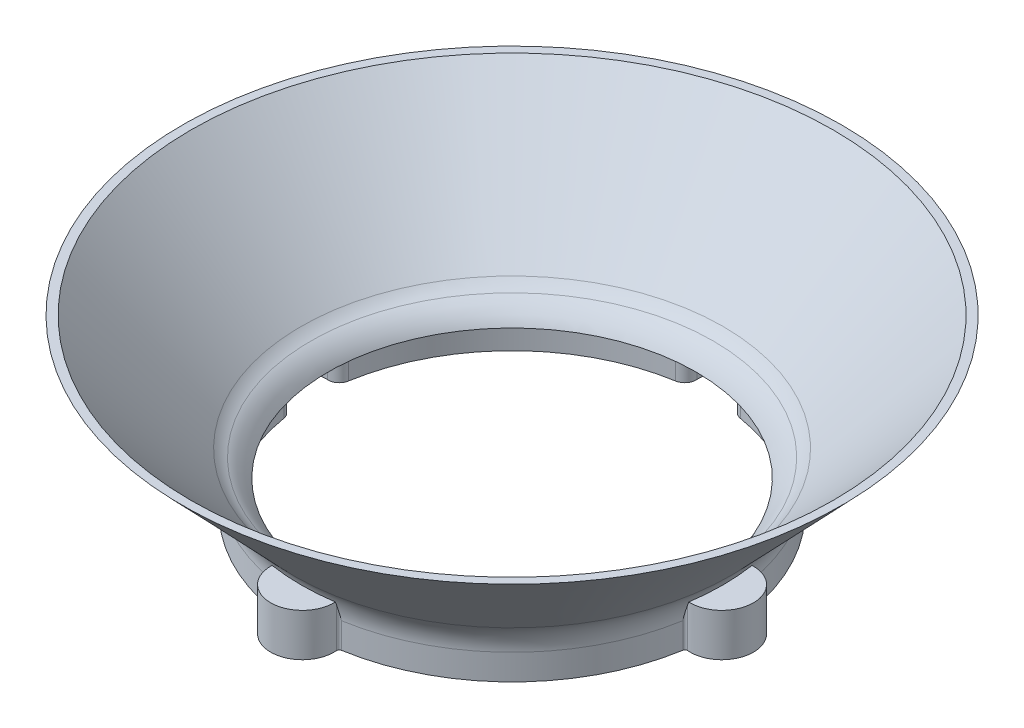
SolidWorks part; units mm, degrees
ref_plane "前视基准面" through (0, 0, 0) normal (0, 0, 1) x (1, 0, 0)
ref_plane "上视基准面" through (0, 0, 0) normal (0, 1, 0) x (1, 0, 0)
ref_plane "右视基准面" through (0, 0, 0) normal (1, 0, 0) x (0, 0, -1)
other "Configuration Table"
sketch "草图1" plane through (0, 0, 0) normal (0, 1, 0) x (1, 0, 0)
  line L0 (-49, 0) -> (0, 0) construction
  circle A0 centre (0, 0) radius 41 construction
  arc A1 (-48.5918, 4.9833) -> (-48.5918, -4.9833) centre (-49, 0) ccw
  circle A2 centre (0, 0) radius 49 construction
  arc A3 (-45.3869, -7.4851) -> (-7.4851, -45.3869) centre (0, 0) ccw
  arc A4 (4.9833, 48.5918) -> (-4.9833, 48.5918) centre (0, 49) ccw
  arc A5 (48.5918, -4.9833) -> (48.5918, 4.9833) centre (49, 0) ccw
  arc A6 (-4.9833, -48.5918) -> (4.9833, -48.5918) centre (0, -49) ccw
  arc A7 (-7.4851, 45.3869) -> (-45.3869, 7.4851) centre (0, 0) ccw
  arc A8 (45.3869, 7.4851) -> (7.4851, 45.3869) centre (0, 0) ccw
  arc A9 (7.4851, -45.3869) -> (45.3869, -7.4851) centre (0, 0) ccw
  arc A10 (-4.9833, -48.5918) -> (-7.4851, -45.3869) centre (-7.9733, -48.3469) ccw
  arc A11 (4.9833, -48.5918) -> (7.4851, -45.3869) centre (7.9733, -48.3469) cw
  arc A12 (48.5918, -4.9833) -> (45.3869, -7.4851) centre (48.3469, -7.9733) ccw
  arc A13 (48.5918, 4.9833) -> (45.3869, 7.4851) centre (48.3469, 7.9733) cw
  arc A14 (4.9833, 48.5918) -> (7.4851, 45.3869) centre (7.9733, 48.3469) ccw
  arc A15 (-4.9833, 48.5918) -> (-7.4851, 45.3869) centre (-7.9733, 48.3469) cw
  arc A16 (-48.5918, -4.9833) -> (-45.3869, -7.4851) centre (-48.3469, -7.9733) cw
  arc A17 (-48.5918, 4.9833) -> (-45.3869, 7.4851) centre (-48.3469, 7.9733) ccw
  point P16 (0, 0)
  point P23 (3.8722, -45.8367)
  point P28 (45.8367, 3.8722)
  point P33 (-3.8722, 45.8367)
  dimension "D1" = 82
  dimension "D3" = 10
  dimension "D2" = 8
  dimension "D4" = 5
  dimension "D6" = 3
  dimension "D5" = 4
sketch "草图2" plane through (0, 0, 0) normal (0, 1, 0) x (1, 0, 0)
  arc A32 (-7.8757, 47.7549) -> (-47.7549, 7.8757) centre (0, 0) ccw
  arc A33 (-48.3959, 7.3753) -> (-47.7549, 7.8757) centre (-48.3469, 7.9733) ccw
  arc A34 (-48.3959, 7.3753) -> (-48.3959, -7.3753) centre (-49, 0) ccw
  arc A35 (-47.7549, -7.8757) -> (-48.3959, -7.3753) centre (-48.3469, -7.9733) ccw
  arc A36 (-47.7549, -7.8757) -> (-7.8757, -47.7549) centre (0, 0) ccw
  arc A37 (-7.3753, -48.3959) -> (-7.8757, -47.7549) centre (-7.9733, -48.3469) ccw
  arc A38 (-7.3753, -48.3959) -> (7.3753, -48.3959) centre (0, -49) ccw
  arc A39 (7.8757, -47.7549) -> (7.3753, -48.3959) centre (7.9733, -48.3469) ccw
  arc A40 (7.8757, -47.7549) -> (47.7549, -7.8757) centre (0, 0) ccw
  arc A42 (48.3959, -7.3753) -> (47.7549, -7.8757) centre (48.3469, -7.9733) ccw
  arc A44 (48.3959, -7.3753) -> (48.3959, 7.3753) centre (49, 0) ccw
  arc A46 (47.7549, 7.8757) -> (48.3959, 7.3753) centre (48.3469, 7.9733) ccw
  arc A48 (47.7549, 7.8757) -> (7.8757, 47.7549) centre (0, 0) ccw
  arc A50 (7.3753, 48.3959) -> (7.8757, 47.7549) centre (7.9733, 48.3469) ccw
  arc A52 (7.3753, 48.3959) -> (-7.3753, 48.3959) centre (0, 49) ccw
  arc A54 (-7.8757, 47.7549) -> (-7.3753, 48.3959) centre (-7.9733, 48.3469) ccw
  arc A56 (-7.5502, 45.7816) -> (-45.7816, 7.5502) centre (0, 0) ccw
  arc A57 (-48.5592, 5.382) -> (-45.7816, 7.5502) centre (-48.3469, 7.9733) ccw
  arc A58 (-48.5592, 5.382) -> (-48.5592, -5.382) centre (-49, 0) ccw
  arc A59 (-45.7816, -7.5502) -> (-48.5592, -5.382) centre (-48.3469, -7.9733) ccw
  arc A60 (-45.7816, -7.5502) -> (-7.5502, -45.7816) centre (0, 0) ccw
  arc A61 (-5.382, -48.5592) -> (-7.5502, -45.7816) centre (-7.9733, -48.3469) ccw
  arc A62 (-5.382, -48.5592) -> (5.382, -48.5592) centre (0, -49) ccw
  arc A63 (7.5502, -45.7816) -> (5.382, -48.5592) centre (7.9733, -48.3469) ccw
  arc A64 (7.5502, -45.7816) -> (45.7816, -7.5502) centre (0, 0) ccw
  arc A65 (48.5592, -5.382) -> (45.7816, -7.5502) centre (48.3469, -7.9733) ccw
  arc A66 (48.5592, -5.382) -> (48.5592, 5.382) centre (49, 0) ccw
  arc A67 (45.7816, 7.5502) -> (48.5592, 5.382) centre (48.3469, 7.9733) ccw
  arc A68 (45.7816, 7.5502) -> (7.5502, 45.7816) centre (0, 0) ccw
  arc A69 (5.382, 48.5592) -> (7.5502, 45.7816) centre (7.9733, 48.3469) ccw
  arc A70 (5.382, 48.5592) -> (-5.382, 48.5592) centre (0, 49) ccw
  arc A71 (-7.5502, 45.7816) -> (-5.382, 48.5592) centre (-7.9733, 48.3469) ccw
  arc A72 (-7.5502, 45.7816) -> (-45.7816, 7.5502) centre (0, 0) ccw
  arc A73 (-48.5592, 5.382) -> (-45.7816, 7.5502) centre (-48.3469, 7.9733) ccw
  arc A74 (-48.5592, 5.382) -> (-48.5592, -5.382) centre (-49, 0) ccw
  arc A75 (-45.7816, -7.5502) -> (-48.5592, -5.382) centre (-48.3469, -7.9733) ccw
  arc A76 (-45.7816, -7.5502) -> (-7.5502, -45.7816) centre (0, 0) ccw
  arc A77 (-5.382, -48.5592) -> (-7.5502, -45.7816) centre (-7.9733, -48.3469) ccw
  arc A78 (-5.382, -48.5592) -> (5.382, -48.5592) centre (0, -49) ccw
  arc A79 (7.5502, -45.7816) -> (5.382, -48.5592) centre (7.9733, -48.3469) ccw
  arc A80 (7.5502, -45.7816) -> (45.7816, -7.5502) centre (0, 0) ccw
  arc A81 (48.5592, -5.382) -> (45.7816, -7.5502) centre (48.3469, -7.9733) ccw
  arc A82 (48.5592, -5.382) -> (48.5592, 5.382) centre (49, 0) ccw
  arc A83 (45.7816, 7.5502) -> (48.5592, 5.382) centre (48.3469, 7.9733) ccw
  arc A84 (45.7816, 7.5502) -> (7.5502, 45.7816) centre (0, 0) ccw
  arc A85 (5.382, 48.5592) -> (7.5502, 45.7816) centre (7.9733, 48.3469) ccw
  arc A86 (5.382, 48.5592) -> (-5.382, 48.5592) centre (0, 49) ccw
  arc A87 (-7.5502, 45.7816) -> (-5.382, 48.5592) centre (-7.9733, 48.3469) ccw
  dimension "D1" = 0.4
  dimension "D2" = 2
ref_plane "基准面1" through (0, 30, 0) normal (0, 1, 0) x (1, 0, 0)
extrude "凸台-拉伸1" add sketch "草图2" against normal blind 10
sketch "草图4" plane through (0, 0, 0) normal (0, 1, 0) x (1, 0, 0)
  circle A13 centre (0, 0) radius 43
  arc A30 (-7.8757, 47.7549) -> (-7.3753, 48.3959) centre (-7.9733, 48.3469) ccw
  arc A31 (-7.8757, 47.7549) -> (-47.7549, 7.8757) centre (0, 0) ccw
  arc A32 (-48.3959, 7.3753) -> (-47.7549, 7.8757) centre (-48.3469, 7.9733) ccw
  arc A33 (-48.3959, 7.3753) -> (-48.3959, -7.3753) centre (-49, 0) ccw
  arc A34 (-47.7549, -7.8757) -> (-48.3959, -7.3753) centre (-48.3469, -7.9733) ccw
  arc A35 (-47.7549, -7.8757) -> (-7.8757, -47.7549) centre (0, 0) ccw
  arc A36 (-7.3753, -48.3959) -> (-7.8757, -47.7549) centre (-7.9733, -48.3469) ccw
  arc A37 (-7.3753, -48.3959) -> (7.3753, -48.3959) centre (0, -49) ccw
  arc A38 (7.8757, -47.7549) -> (7.3753, -48.3959) centre (7.9733, -48.3469) ccw
  arc A39 (7.8757, -47.7549) -> (47.7549, -7.8757) centre (0, 0) ccw
  arc A40 (48.3959, -7.3753) -> (47.7549, -7.8757) centre (48.3469, -7.9733) ccw
  arc A41 (48.3959, -7.3753) -> (48.3959, 7.3753) centre (49, 0) ccw
  arc A42 (47.7549, 7.8757) -> (48.3959, 7.3753) centre (48.3469, 7.9733) ccw
  arc A43 (47.7549, 7.8757) -> (7.8757, 47.7549) centre (0, 0) ccw
  arc A44 (7.3753, 48.3959) -> (7.8757, 47.7549) centre (7.9733, 48.3469) ccw
  arc A45 (7.3753, 48.3959) -> (-7.3753, 48.3959) centre (0, 49) ccw
  arc A46 (-7.8757, 47.7549) -> (-7.3753, 48.3959) centre (-7.9733, 48.3469) ccw
  arc A47 (-7.8757, 47.7549) -> (-47.7549, 7.8757) centre (0, 0) ccw
  arc A48 (-48.3959, 7.3753) -> (-47.7549, 7.8757) centre (-48.3469, 7.9733) ccw
  arc A49 (-48.3959, 7.3753) -> (-48.3959, -7.3753) centre (-49, 0) ccw
  arc A50 (-47.7549, -7.8757) -> (-48.3959, -7.3753) centre (-48.3469, -7.9733) ccw
  arc A51 (-47.7549, -7.8757) -> (-7.8757, -47.7549) centre (0, 0) ccw
  arc A52 (-7.3753, -48.3959) -> (-7.8757, -47.7549) centre (-7.9733, -48.3469) ccw
  arc A53 (-7.3753, -48.3959) -> (7.3753, -48.3959) centre (0, -49) ccw
  arc A54 (7.8757, -47.7549) -> (7.3753, -48.3959) centre (7.9733, -48.3469) ccw
  arc A55 (7.8757, -47.7549) -> (47.7549, -7.8757) centre (0, 0) ccw
  arc A56 (48.3959, -7.3753) -> (47.7549, -7.8757) centre (48.3469, -7.9733) ccw
  arc A57 (48.3959, -7.3753) -> (48.3959, 7.3753) centre (49, 0) ccw
  arc A58 (47.7549, 7.8757) -> (48.3959, 7.3753) centre (48.3469, 7.9733) ccw
  arc A59 (47.7549, 7.8757) -> (7.8757, 47.7549) centre (0, 0) ccw
  arc A60 (7.3753, 48.3959) -> (7.8757, 47.7549) centre (7.9733, 48.3469) ccw
  arc A61 (7.3753, 48.3959) -> (-7.3753, 48.3959) centre (0, 49) ccw
  dimension "D1" = 86
  dimension "D2" = 0
extrude "凸台-拉伸2" add sketch "草图4" against normal blind 3
sketch "草图7" plane through (0, 0, 0) normal (1, 0, 0) x (0, 0, -1)
  line L0 (-46.4, 0) -> (-48.4, 0)
  line L1 (-48.4, 0) -> (-77, 30)
  line L2 (-77, 30) -> (-75, 30)
  line L3 (-75, 30) -> (-46.4, 0)
  line L4 (0, 0) -> (0, 30) construction
  line L5 (-75, 30) -> (0, 30) construction
  dimension "D1" = 2
  dimension "D2" = 30
  dimension "D3" = 75
  dimension "D4" = 46.4
revolve "旋转1" add sketch "草图7" angle 360 about L4
fillet "圆角1" radius 10 2 edges at (0, 0, -46.4) (-34.224, 0, -34.224)
fillet "圆角2" radius 10 1 edges at (0, 0, 43)
